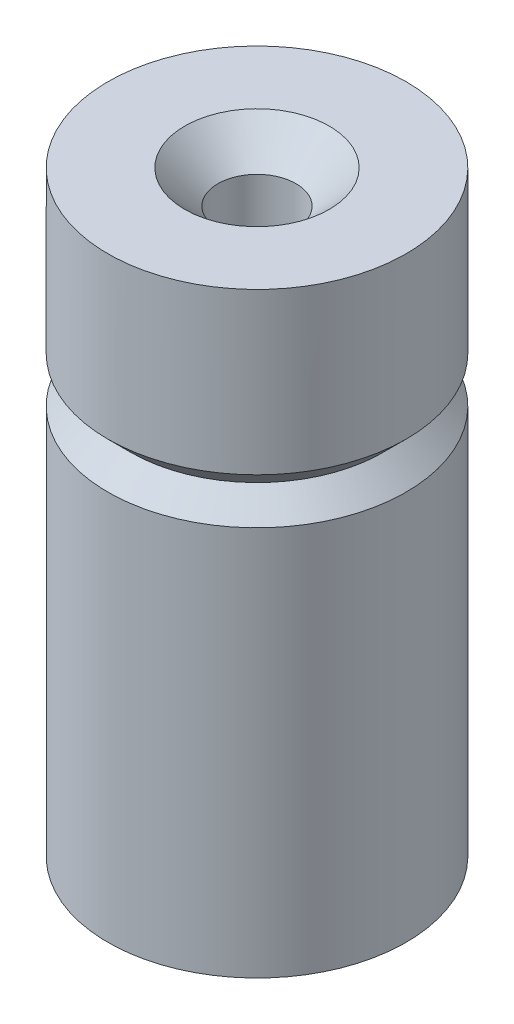
SolidWorks part; units mm, degrees
material "Сплав 2024"
ref_plane "Спереди" through (0, 0, 0) normal (0, 0, 1) x (1, 0, 0)
ref_plane "Сверху" through (0, 0, 0) normal (0, 1, 0) x (1, 0, 0)
ref_plane "Справа" through (0, 0, 0) normal (1, 0, 0) x (0, 0, -1)
sketch "Эскиз1" plane through (0, 0, 0) normal (0, 1, 0) x (1, 0, 0)
  circle A0 centre (0, 0) radius 6.5
  dimension "D1" = 13
extrude "Бобышка-Вытянуть1" add sketch "Эскиз1" along normal blind 26
sketch "Эскиз2" plane through (0, 0, 0) normal (0, -1, 0) x (1, 0, 0)
  circle A0 centre (0, 0) radius 2.85
  dimension "D1" = 5.7
extrude "Вырез-Вытянуть1" cut sketch "Эскиз2" against normal blind 3.5
hole_wizard "Зенковка для  винта с плоской головкой M32" positions "Эскиз4" profile "Эскиз3" countersink size "M3" standard "Ansi Metric" end condition through all
sketch "Эскиз4" plane through (0, 26, 0) normal (0, 1, 0) x (1, 0, 0)
  point P0 (0, 0)
sketch "Эскиз3" plane through (0, 26, 0) normal (1, 0, 0) x (0, 0, 1)
  line L0 (0, 0) -> (0, 26)
  line L1 (0, 26) -> (1.7, 26)
  line L2 (1.7, 26) -> (1.7, 1.45)
  line L3 (1.7, 1.45) -> (3.15, 0)
  line L5 (3.15, 0) -> (0, 0)
  line L6 (-1.7, 1.45) -> (-3.15, 0) construction
  line L11 (0, -6.35) -> (0, 107.95) construction
  dimension "Диаметр сквозного отверстия" = 3.4
  dimension "Глубина сквозного отверстия" = 26
  dimension "Диаметр передней зенковки" = 6.3
  dimension "Угол передней зенковки" = 90
ref_plane "Плоскость1" through (0, 18, 0) normal (0, -1, 0) x (-1, 0, 0)
sketch "Эскиз5" plane through (0, 18, 0) normal (0, -1, 0) x (-1, 0, 0)
  line L0 (0, 6.5) -> (0, -6.5) construction
  circle A0 centre (0, 0) radius 6.5
  circle A1 centre (0, 0) radius 6.5 construction
ref_plane "Плоскость2" through (0, 0, 0) normal (1, 0, 0) x (0, 0, -1)
sketch "Эскиз6" plane through (0, 0, 0) normal (1, 0, 0) x (0, 0, -1)
  line L0 (6.5, 19) -> (5.5, 18)
  line L1 (6.5, 0) -> (6.5, 26) construction
  line L2 (6.5, 18) -> (-6.5, 18) construction
  line L3 (5.5, 18) -> (6.5, 17)
  line L4 (6.5, 0) -> (6.5, 26) construction
  line L5 (6.5, 17) -> (6.5, 19)
  dimension "D1" = 90
  dimension "D2" = 1
  dimension "D3" = 45
sweep "Вырез-По траектории2" cut profiles "Эскиз6" path "Эскиз5"
